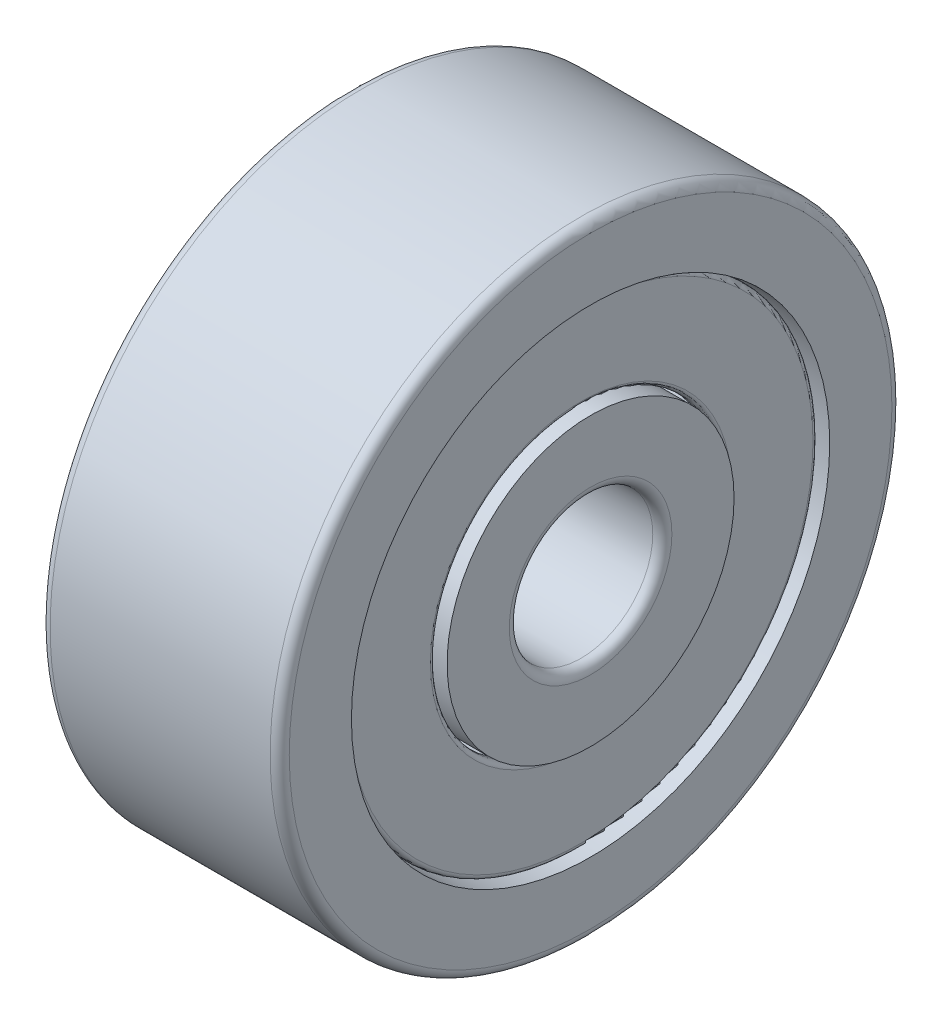
SolidWorks part; units mm, degrees
ref_plane "Plane1" through (0, 0, 0) normal (0, 0, 1) x (1, 0, 0)
ref_plane "Plane2" through (0, 0, 0) normal (0, 1, 0) x (1, 0, 0)
ref_plane "Plane3" through (0, 0, 0) normal (1, 0, 0) x (0, 0, -1)
sketch "Clipboard" plane through (0, 0, 0) normal (0, 0, 1) x (1, 0, 0)
  line L0 (-10, 0) -> (10, 0) construction
  line L1 (0, 0) -> (22.1431, -3.112)
  line L2 (0, 0) -> (3.9994, -0.0698)
  line L3 (0, 0) -> (22.3573, 0.3902)
  line L4 (0, 0) -> (-22.3573, -0.3902)
  dimension "BallCLRad" = 4
sketch "CagSpiSke" plane through (0, 0, 0) normal (0, 0, 1) x (1, 0, 0)
  line L0 (0.15, 3.75) -> (0.15, 4.25)
  line L1 (0.15, 4.25) -> (-0.15, 4.25)
  line L2 (-0.15, 4.25) -> (-0.15, 3.75)
  line L3 (-0.15, 3.75) -> (0.15, 3.75)
  line L4 (-20.6375, 0) -> (20.6375, 0) construction
  line L5 (0, 0) -> (0, 23.7692) construction
  dimension "OD" = 8.5
  dimension "ID" = 7.5
revolve "CageSpine" add sketch "CagSpiSke" angle 0.001 about L4 reverse direction yes
ref_axis "Axis1" through (-50, 0, 0) along (1, 0, 0)
sketch "CagBalSke" plane through (0, 0, 0) normal (0, 0, 1) x (1, 0, 0)
  line L0 (-1.65, 4) -> (1.65, 4)
  line L1 (-1.905, 4) -> (1.905, 4) construction
  line L2 (-10, 0) -> (10, 0) construction
  line L3 (0, 0) -> (0, 24) construction
  arc A0 (1.65, 4) -> (-1.65, 4) centre (0, 4) cw
  dimension "BallCLRad" = 4
revolve "CageBall" [suppressed] add sketch "CagBalSke" angle 360 about L1 reverse direction yes
pattern_circular "CageBalls" [suppressed] count 8 every 45 about axis through (-50, 0, 0) along (1, 0, 0)
sketch "CagTrmODSke" plane through (0, 0, 0) normal (0, 0, 1) x (1, 0, 0)
  line L0 (1.651, 4.25) -> (1.651, 5.651)
  line L1 (1.651, 5.651) -> (-1.651, 5.651)
  line L2 (-1.651, 5.651) -> (-1.651, 4.25)
  line L3 (-1.651, 4.25) -> (1.651, 4.25)
  line L4 (-20.6375, 0) -> (20.6375, 0) construction
  line L5 (0, 0) -> (0, 25) construction
  dimension "Width" = 3.302
  dimension "ID" = 8.5
  dimension "OD" = 11.302
revolve "CageTrimOD" [suppressed] cut sketch "CagTrmODSke" angle 360 about L4 reverse direction yes
sketch "CagTrmIDSke" plane through (0, 0, 0) normal (0, 0, 1) x (1, 0, 0)
  line L0 (1.651, 2.351) -> (1.651, 3.75)
  line L1 (1.651, 3.75) -> (-1.651, 3.75)
  line L2 (-1.651, 3.75) -> (-1.651, 2.351)
  line L3 (-1.651, 2.351) -> (1.651, 2.351)
  line L4 (-20.6375, 0) -> (20.6375, 0) construction
  line L5 (0, 0) -> (0, 25) construction
  dimension "Width" = 3.302
  dimension "ID" = 4.702
  dimension "OD" = 7.5
revolve "CageTrimID" [suppressed] cut sketch "CagTrmIDSke" angle 360 about L4 reverse direction yes
sketch "BalSimSke" plane through (0, 0, 0) normal (0, 0, 1) x (1, 0, 0)
  line L0 (-10, 0) -> (10, 0) construction
  line L1 (-10, 4) -> (10, 4) construction
  line L2 (0, 0) -> (0, 23) construction
  circle A0 centre (0, 4) radius 1.5
  dimension "BallCLRad" = 4
  dimension "Ball_diameter" = 3
revolve "BallsSimplified" [suppressed] add sketch "BalSimSke" angle 360 about L0
sketch "BalDetSke" plane through (0, 0, 0) normal (0, 0, 1) x (1, 0, 0)
  line L0 (-1.5, 4) -> (1.5, 4)
  line L1 (-1.905, 4) -> (1.905, 4) construction
  line L2 (0, 0) -> (0, 25) construction
  arc A0 (1.5, 4) -> (-1.5, 4) centre (0, 4) cw
  dimension "BallCLRad" = 4
  dimension "Ball_diameter" = 3
revolve "BallDetailed" add sketch "BalDetSke" angle 360 about L1 reverse direction yes
sketch "InnRacSke" plane through (0, 0, 0) normal (0, 0, 1) x (1, 0, 0)
  line L0 (-1.0843, 3) -> (-2.5, 3)
  line L1 (-2.5, 3) -> (-2.5, 1.7)
  line L2 (-2.3, 1.5) -> (2.3, 1.5)
  line L3 (2.5, 1.7) -> (2.5, 3)
  line L4 (2.5, 3) -> (1.0843, 3)
  line L5 (-20.6375, 0) -> (20.6375, 0) construction
  line L6 (0, 0) -> (0, 30) construction
  arc A0 (-2.5, 1.7) -> (-2.3, 1.5) centre (-2.3, 1.7) ccw
  arc A1 (2.3, 1.5) -> (2.5, 1.7) centre (2.3, 1.7) ccw
  arc A2 (1.0843, 3) -> (-1.0843, 3) centre (0, 4) cw
  dimension "BallCLRad" = 4
  dimension "Fillet_radius" = 0.2
  dimension "Ball_diameter" = 2.95
  dimension "ID" = 3
  dimension "OD" = 6
  dimension "Width" = 5
revolve "InnerRace" add sketch "InnRacSke" angle 360 about L5 reverse direction yes
sketch "OutRacSke" plane through (0, 0, 0) normal (0, 0, 1) x (1, 0, 0)
  line L0 (-1.0843, 5) -> (-2.5, 5)
  line L1 (-2.5, 5) -> (-2.5, 6.3)
  line L2 (-2.3, 6.5) -> (2.3, 6.5)
  line L3 (2.5, 6.3) -> (2.5, 5)
  line L4 (2.5, 5) -> (1.0843, 5)
  line L5 (-20.6375, 0) -> (20.6375, 0) construction
  line L6 (0, 0) -> (0, 30) construction
  arc A0 (-2.5, 6.3) -> (-2.3, 6.5) centre (-2.3, 6.3) cw
  arc A1 (2.3, 6.5) -> (2.5, 6.3) centre (2.3, 6.3) cw
  arc A2 (1.0843, 5) -> (-1.0843, 5) centre (0, 4) ccw
  dimension "BallCLRad" = 4
  dimension "Fillet_radius" = 0.2
  dimension "Ball_diameter" = 2.95
  dimension "Width" = 5
revolve "OuterRace" add sketch "OutRacSke" angle 360 about L5 reverse direction yes
pattern_circular "BallsDetailed" count 8 every 45 about axis through (-50, 0, 0) along (1, 0, 0) of "BallDetailed"
sketch "Esquisse1" plane through (2.5, 0, 0) normal (1, 0, 0) x (0, 0, -1)
  circle A5 centre (0, 0) radius 3.05
  circle A6 centre (0, 0) radius 3.05
  circle A8 centre (0, 0) radius 4.95
  circle A9 centre (0, 0) radius 4.95
  dimension "D2" = 0.05
  dimension "D3" = 0.05
extrude "Boss.-Extru.1" add sketch "Esquisse1" against normal blind 0.2 from offset 0.2 separate body offset against normal yes
fillet "Congé1" radius 0.1 2 edges at (2.3, 0, -4.95) (2.3, 0, -3.05)
mirror "Symétrie2" about plane through (0, 0, 0) normal (1, 0, 0) of bodies 106
equation "\"BallCLRad@Clipboard\" = ( \"OD@OutRacSke\" + \"ID@InnRacSke\" ) / 4"
equation "\"BallCLRad@BalSimSke\" = \"BallCLRad@Clipboard\""
equation "\"BallCLRad@BalDetSke\" = \"BallCLRad@Clipboard\""
equation "\"BallCLRad@InnRacSke\" = \"BallCLRad@Clipboard\""
equation "\"BallCLRad@OutRacSke\" = \"BallCLRad@Clipboard\""
equation "\"Ball_diameter@InnRacSke\" = \"Ball_diameter@BalDetSke\" - 0.05"
equation "\"Ball_diameter@OutRacSke\" = \"Ball_diameter@BalDetSke\" - 0.05"
equation "\"Ball_diameter@BalSimSke\" = \"Ball_diameter@BalDetSke\""
equation "\"Width@OutRacSke\" = \"Width@InnRacSke\""
equation "\"Fillet_radius@OutRacSke\" = \"Fillet_radius@InnRacSke\""
equation "\"Max_count@Clipboard\" = int( 3.14159265 / atn(( \"Ball_diameter@BalDetSke\" / 2) / sqr( \"BallCLRad@Clipboard\"  *  \"BallCLRad@Clipboard\" - ( \"Ball_diameter@BalDetSke\" / 2) *  ( \"Ball_diameter@BalDetSke\" / 2))))"
equation "\"Max_count@Clipboard\" = ((sgn( \"Max_count@Clipboard\" - \"Count@Clipboard\" )-1)*( \"Max_count@Clipboard\" - \"Count@Clipboard\" ))/-2+ \"Count@Clipboard\""
equation "\"Count@BallsDetailed\" = int( \"Show_count@Clipboard\" ) "
equation "\"Count@BallsDetailed\" = ((sgn( \"Count@BallsDetailed\" - \"Max_count@Clipboard\" )-1)*( \"Count@BallsDetailed\" - \"Max_count@Clipboard\" ))/-2+ \"Max_count@Clipboard\""
equation "\"Count@BallsDetailed\" = ((sgn( \"Count@BallsDetailed\" - \"Min_count@Clipboard\" )+1)*( \"Count@BallsDetailed\" - \"Min_count@Clipboard\"))/2 +\"Min_count@Clipboard\""
equation "\"Angle@BallsDetailed\" = 360.0 / \"Max_count@Clipboard\""
equation "\"BallCLRad@CagBalSke\" = \"BallCLRad@Clipboard\""
equation "\"Count@CageBalls\" = \"Count@BallsDetailed\""
equation "\"Angle@CageBalls\" = \"Angle@BallsDetailed\""
equation "\"Angle@CageSpine\" =  \"Angle@CageBalls\" * ( \"Count@CageBalls\" -1 + int( \"Count@CageBalls\" / \"Max_count@Clipboard\" ) )  + 0.001 -  int( \"Count@CageBalls\" / \"Max_count@Clipboard\" ) * 0.001"
equation "\"Angle@CageSpine\" =  \"Angle@CageSpine\" * int( \"Min_count@Clipboard\" / 2) + int(1 / \"Min_count@Clipboard\")  * 0.001"
equation "\"CageWallOD@CagBalSke\" =  \"Ball_diameter@BalDetSke\" * 1.1"
equation "\"Thickness@CagSpiSke\" =  \"Ball_diameter@BalDetSke\" * 0.1"
equation "\"OD@CagTrmODSke\" = \"BallCLRad@Clipboard\" * 2 + \"CageWallOD@CagBalSke\" + 0.002"
equation "\"ID@CagTrmODSke\" = \"BallCLRad@Clipboard\" * 2 + \"Ball_diameter@BalDetSke\" / 6"
equation "\"OD@CagTrmIDSke\" = \"BallCLRad@Clipboard\" * 2 - \"Ball_diameter@BalDetSke\" / 6"
equation "\"ID@CagTrmIDSke\" = \"BallCLRad@Clipboard\" * 2 - \"CageWallOD@CagBalSke\" + 0.002"
equation "\"OD@CagSpiSke\" = \"ID@CagTrmODSke\""
equation "\"ID@CagSpiSke\" = \"OD@CagTrmIDSke\""
equation "\"Width@CagTrmODSke\" = \"CageWallOD@CagBalSke\" + 0.002"
equation "\"Width@CagTrmIDSke\" = \"CageWallOD@CagBalSke\" + 0.002"
